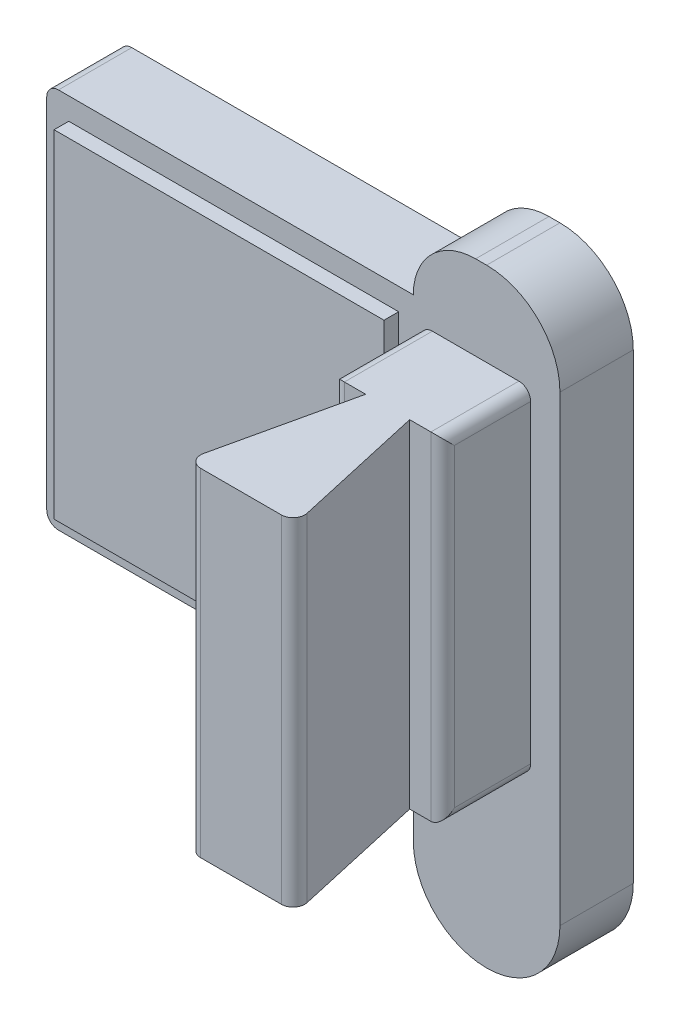
SolidWorks part; units mm, degrees
material "ABS"
ref_plane "Front" through (0, 0, 0) normal (0, 0, 1) x (1, 0, 0)
ref_plane "Top" through (0, 0, 0) normal (0, 1, 0) x (1, 0, 0)
ref_plane "Right" through (0, 0, 0) normal (1, 0, 0) x (0, 0, -1)
sketch "Sketch1" plane through (0, 0, 0) normal (0, 0, 1) x (1, 0, 0)
  line L0 (0, 0) -> (0, 26) construction
  line L1 (-4.25, 0) -> (-4.25, 26)
  line L2 (4.25, 0) -> (4.25, 26)
  line L4 (-2.25, 3) -> (2.25, 3)
  line L5 (-2.25, 3) -> (-2.25, 23)
  line L6 (-2.25, 23) -> (2.25, 23)
  line L7 (2.25, 3) -> (2.25, 23)
  arc A0 (-4.25, 0) -> (4.25, 0) centre (0, 0) ccw
  arc A1 (4.25, 26) -> (-4.25, 26) centre (0, 26) ccw
  circle A2 centre (0, 26) radius 1.45
  circle A3 centre (0, 0) radius 1.45
  point P3 (0, 13)
  point P12 (0, 23)
  point P17 (4.25, 13)
  point P21 (2.25, 13)
  dimension "D1" = 2.9
  dimension "D2" = 26
  dimension "D3" = 4.5
  dimension "D4" = 2
  dimension "D5" = 20
extrude "Boss-Extrude1" add sketch "Sketch1" along normal blind 5
sketch "Sketch2" plane through (0, 0, 5) normal (0, 0, 1) x (1, 0, 0)
  line L0 (2.25, 23) -> (-2.25, 23) construction
  line L1 (2.25, 23) -> (-2.25, 23)
  line L2 (-2.25, 3) -> (2.25, 3) construction
  line L3 (2.25, 3) -> (2.25, 23) construction
  line L4 (-2.25, 23) -> (-2.25, 3) construction
  line L5 (-2.25, 3) -> (2.25, 3)
  line L6 (2.25, 3) -> (2.25, 23)
  line L7 (-2.25, 23) -> (-2.25, 3)
  line L8 (3.75, 1.5) -> (3.75, 24.5)
  line L9 (3.75, 24.5) -> (-3.75, 24.5)
  line L10 (-3.75, 24.5) -> (-3.75, 1.5)
  line L11 (-3.75, 1.5) -> (3.75, 1.5)
  dimension "D1" = 1.5
extrude "Boss-Extrude2" add sketch "Sketch2" along normal blind 5
sketch "Sketch3" plane through (0, 0, 10) normal (0, 0, 1) x (1, 0, 0)
  line L1 (-3.75, 24.5) -> (3.75, 24.5)
  line L2 (-3.75, 24.5) -> (-3.75, 1.5)
  line L3 (-3.75, 1.5) -> (3.75, 1.5)
  line L4 (3.75, 24.5) -> (3.75, 1.5)
extrude "Boss-Extrude3" add sketch "Sketch3" along normal blind 1
sketch "Sketch4" plane through (0, 0, 11) normal (0, 0, 1) x (1, 0, 0)
  line L1 (-3.75, 1.5) -> (3.75, 1.5) construction
  line L2 (-3.75, 1.5) -> (-3.75, 24.5) construction
  line L3 (-3.75, 24.5) -> (3.75, 24.5) construction
  line L4 (3.75, 1.5) -> (3.75, 24.5) construction
  line L5 (-3.75, 1.5) -> (3.75, 24.5) construction
  line L6 (-3.75, 24.5) -> (3.75, 1.5) construction
  point P0 (0, 13)
ref_axis "Axis1" through (0, 13, 11) along (0, 0, 1)
ref_plane "Plane1" through (0, 0, 0) normal (1, 0, 0) x (0, 0, -1)
sketch "Sketch6" plane through (0, 1.5, 0) normal (0, -1, 0) x (1, 0, 0)
  circle A0 centre (0, 7.1539) radius 1.25
  dimension "D1" = 2.5
extrude "Cut-Extrude1" cut sketch "Sketch6" against normal up to next
sketch "Sketch7" plane through (-4.25, 0, 0) normal (-1, 0, 0) x (0, 0, 1)
  line L1 (5, 26) -> (0, 26)
  line L2 (5, 26) -> (5, 0)
  line L3 (5, 0) -> (0, 0)
  line L4 (0, 26) -> (0, 0)
extrude "Boss-Extrude4" add sketch "Sketch7" along normal blind 25
sketch "Sketch8" plane through (0, 0, 5) normal (0, 0, 1) x (1, 0, 0)
  line L0 (3.75, 24.5) -> (-3.75, 24.5) construction
  line L1 (-27.75, 24.5) -> (-5.25, 24.5)
  line L2 (-27.75, 24.5) -> (-27.75, 1.5)
  line L3 (-27.75, 1.5) -> (-5.25, 1.5)
  line L4 (-5.25, 24.5) -> (-5.25, 1.5)
  line L5 (-3.75, 1.5) -> (3.75, 1.5) construction
  line L6 (-29.25, 0) -> (-29.25, 26) construction
  line L7 (-3.75, 24.5) -> (-3.75, 1.5) construction
  dimension "D1" = 1.5
  dimension "D2" = 1.5
extrude "Boss-Extrude5" add sketch "Sketch8" along normal blind 1
sketch "Sketch10" plane through (0, 1.5, 0) normal (0, -1, 0) x (1, 0, 0)
  line L0 (-1.5, 11) -> (1.5, 11)
  line L1 (-3.75, 11) -> (3.75, 11) construction
  line L2 (1.5, 11) -> (3.75, 21)
  line L3 (3.75, 21) -> (-3.75, 21)
  line L4 (-3.75, 21) -> (-1.5, 11)
  line L5 (0, 11) -> (0, 21) construction
  line L6 (-3.75, 11) -> (-3.75, 21) construction
  line L7 (3.75, 21) -> (3.75, 11) construction
  dimension "D1" = 3
  dimension "D2" = 10
extrude "Boss-Extrude6" add sketch "Sketch10" against normal up to surface (23 mm away) up to face at (0, 24.5, 8)
fillet "Fillet1" radius 0.8 10 edges at (-3.75, 24.5, 8) (3.75, 24.5, 8) (3.75, 1.5, 8) (-3.75, 1.5, 8) (-29.25, 26, 2.5) (-29.25, 0, 2.5) (-3.75, 13, 11) (3.75, 13, 11) (3.75, 13, 21) (-3.75, 13, 21)
sketch "Sketch11" plane through (0, 0, 5) normal (0, 0, 1) x (1, 0, 0)
  line L0 (-4.25, 0) -> (-4.25, -11.2626)
  line L1 (-4.25, -11.2626) -> (4.25, -11.2626)
  line L2 (4.25, -11.2626) -> (4.25, 0)
  line L3 (0, 0) -> (1.6, 0) construction
  line L4 (1.6, 0) -> (1.6, -6.45) construction
  arc A0 (-4.25, 0) -> (4.25, 0) centre (0, 0) ccw construction
  arc A1 (4.25, 0) -> (-4.25, 0) centre (0, 0) cw
  circle A2 centre (1.6, -6.45) radius 1.55 construction
  dimension "D1" = 3.1
  dimension "D2" = 1.6
  dimension "D3" = 6.45
extrude "Boss-Extrude7" add sketch "Sketch11" against normal up to surface (5 mm away) up to face at (1.45, 0, 0)
sketch "Sketch12" plane through (0, 0, 0) normal (0, 0, -1) x (-1, 0, 0)
  line L0 (0, 0) -> (-1.6, 0) construction
  line L1 (-1.6, 0) -> (-1.6, -6.45) construction
  circle A0 centre (-1.6, -6.45) radius 3.15
  dimension "D1" = 6.3
  dimension "D2" = 1.6
  dimension "D3" = 6.45
sketch "Sketch13" plane through (0, 0, 5) normal (0, 0, 1) x (1, 0, 0)
  line L0 (4.25, -11.2626) -> (5.75, -11.2626)
  line L1 (5.75, -11.2626) -> (5.75, 30.25)
  line L2 (5.75, 30.25) -> (0, 30.25)
  line L3 (4.25, -11.2626) -> (4.25, 26)
  arc A0 (4.25, 26) -> (-4.25, 26) centre (0, 26) ccw construction
  arc A1 (4.25, 26) -> (0, 30.25) centre (0, 26) ccw
  dimension "D1" = 1.5
extrude "Boss-Extrude8" add sketch "Sketch13" against normal up to surface (5 mm away) up to face at (1.45, 0, 0)
extrude "Cut-Extrude2" cut sketch "Sketch12" against normal blind 3.1
fillet "Fillet2" radius 5 3 edges at (5.75, 30.25, 2.5) (5.75, -11.2626, 2.5) (-4.25, -11.2626, 2.5)
sketch "Sketch14" plane through (0, 0, 5) normal (0, 0, 1) x (1, 0, 0)
  circle A0 centre (0, 26) radius 1.45 construction
  circle A1 centre (0, 0) radius 1.45 construction
  circle A2 centre (0, 26) radius 1.45
  circle A3 centre (0, 0) radius 1.45
extrude "Boss-Extrude9" add sketch "Sketch14" against normal blind 0.4
